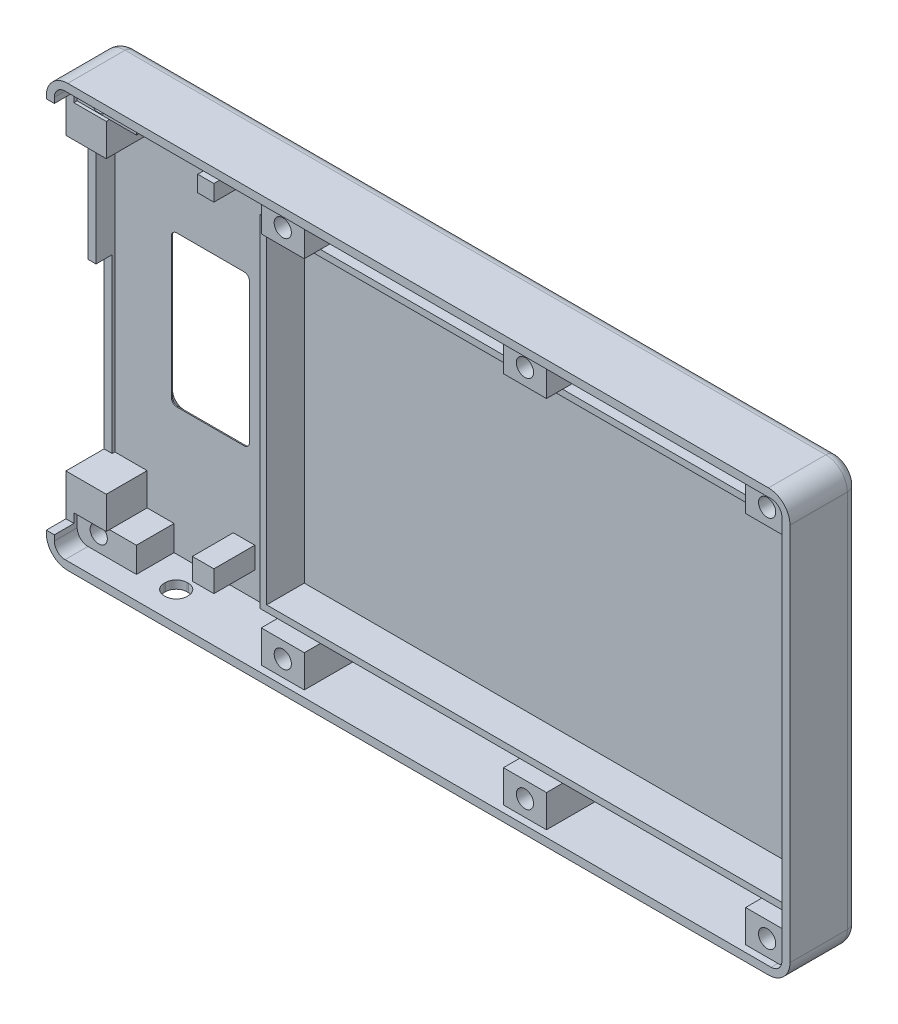
SolidWorks part; units mm, degrees
ref_plane "Plan de face" through (0, 0, 0) normal (0, 0, 1) x (1, 0, 0)
ref_plane "Plan de dessus" through (0, 0, 0) normal (0, 1, 0) x (1, 0, 0)
ref_plane "Plan de droite" through (0, 0, 0) normal (1, 0, 0) x (0, 0, -1)
sketch "Esquisse1" plane through (0, 0, 0) normal (0, 0, 1) x (1, 0, 0)
  line L0 (135.2, 69.4) -> (34, 69.4)
  line L1 (0, 0) -> (135.2, 0)
  line L2 (0, 0) -> (0, 75.4)
  line L3 (0, 75.4) -> (135.2, 75.4)
  line L4 (135.2, 0) -> (135.2, 75.4)
  line L5 (34, 69.4) -> (34, 6)
  line L6 (34, 6) -> (135.2, 6)
  line L7 (135.2, 68.2) -> (35.2, 68.2)
  line L8 (35.2, 68.2) -> (35.2, 7.2)
  line L9 (35.2, 7.2) -> (135.2, 7.2)
  line L10 (-19.055, 37.7) -> (204.5006, 37.7) construction
  line L11 (-1.5, 76.9) -> (136.7, 76.9)
  line L12 (-1.5, 76.9) -> (-1.5, -1.5)
  line L13 (-1.5, -1.5) -> (136.7, -1.5)
  line L14 (136.7, 76.9) -> (136.7, -1.5)
  line L15 (0, 72.1) -> (0, 70.7)
  line L16 (26, 70.7) -> (0, 70.7)
  line L17 (26, 70.7) -> (26, 4.7)
  line L18 (26, 4.7) -> (0, 4.7)
  line L19 (0, 70.7) -> (0, 4.7)
  line L20 (1.4, 69.3) -> (24.6, 69.3)
  line L21 (1.4, 69.3) -> (1.4, 6.1)
  line L22 (1.4, 6.1) -> (24.6, 6.1)
  line L23 (24.6, 69.3) -> (24.6, 6.1)
  line L24 (0, 72.1) -> (27.4, 72.1)
  line L25 (0, 3.3) -> (0, 4.7)
  line L26 (0, 3.3) -> (27.4, 3.3)
  line L27 (27.4, 72.1) -> (27.4, 3.3)
  line L28 (127.2, 75.4) -> (127.2, 69.4)
  line L29 (0, 4.7) -> (6, 4.7)
  line L30 (0, 4.7) -> (0, 10.7)
  line L31 (0, 10.7) -> (6, 10.7)
  line L32 (6, 4.7) -> (6, 10.7)
  line L33 (26, 4.7) -> (22, 4.7)
  line L34 (26, 4.7) -> (26, 8.7)
  line L35 (26, 8.7) -> (22, 8.7)
  line L36 (22, 4.7) -> (22, 8.7)
  line L37 (0, 70.7) -> (6, 70.7)
  line L38 (0, 70.7) -> (0, 64.7)
  line L39 (0, 64.7) -> (6, 64.7)
  line L40 (6, 70.7) -> (6, 64.7)
  line L41 (26, 70.7) -> (23, 70.7)
  line L42 (26, 70.7) -> (26, 67.7)
  line L43 (26, 67.7) -> (23, 67.7)
  line L44 (23, 70.7) -> (23, 67.7)
  line L45 (90.2, 75.4) -> (90.2, 69.4)
  line L46 (82.2, 75.4) -> (82.2, 69.4)
  line L47 (45.2, 75.4) -> (45.2, 69.4)
  line L48 (37.2, 75.4) -> (37.2, 69.4)
  line L49 (127.2, 0) -> (127.2, 6)
  line L50 (90.2, 0) -> (90.2, 6)
  line L51 (82.2, 0) -> (82.2, 6)
  line L52 (45.2, 0) -> (45.2, 6)
  line L53 (37.2, 0) -> (37.2, 6)
  circle A0 centre (131.2, 72.4) radius 1.25
  circle A3 centre (86.2, 72.4) radius 1.25
  circle A5 centre (41.2, 72.4) radius 1.25
  circle A6 centre (131.2, 3) radius 1.25
  circle A8 centre (86.2, 3) radius 1.25
  circle A11 centre (41.2, 3) radius 1.25
  dimension "D12" = 2.5
  dimension "D13" = 4
  dimension "D1" = 1.5
  dimension "D3" = 1.2
  dimension "D4" = 1.2
  dimension "D5" = 1.2
  dimension "D6" = 61
  dimension "D7" = 6
  dimension "D8" = 100
  dimension "D9" = 1.5
  dimension "D10" = 1.5
  dimension "D11" = 1.5
  dimension "D15" = 30.5
  dimension "D16" = 30.5
  dimension "D17" = 3
  dimension "D18" = 66
  dimension "D19" = 26
  dimension "D20" = 33
  dimension "D21" = 33
  dimension "D22" = 8
  dimension "D23" = 1.4
  dimension "D24" = 1.4
  dimension "D25" = 1.4
  dimension "D26" = 1.4
  dimension "D27" = 1.4
  dimension "D28" = 0
  dimension "D29" = 1.4
  dimension "D30" = 1.4
  dimension "D31" = 4
  dimension "D32" = 0
  dimension "D33" = 0
  dimension "D34" = 6
  dimension "D35" = 6
  dimension "D36" = 4
  dimension "D37" = 4
  dimension "D38" = 6
  dimension "D39" = 6
  dimension "D40" = 3
  dimension "D41" = 3
  dimension "D42" = 4
  dimension "D43" = 4
  dimension "D44" = 4
  dimension "D45" = 4
  dimension "D46" = 6
  dimension "D47" = 45
  dimension "D14" = 3
extrude "Boss.-Extru.1" add sketch "Esquisse1" along normal blind 12.65 contours L12 L10 L2 L3 L4 L14 L11 | L10 L12 L13 L14 L4 L1 L2 region at (136.6365, 72.4, 0) region at (135.95, 36.2635, 0)
extrude "Boss.-Extru.2" add sketch "Esquisse1<4>" along normal blind 1.4 contours L3 L4 L1 L2
sketch "Esquisse1<4>" plane through (0, 0, 0) normal (0, 0, 1) x (1, 0, 0) same geometry as "Esquisse1"
extrude "Boss.-Extru.5" add sketch "Esquisse1<5>" along normal blind 10 from surface separate body contours A5 | A3 | A0 | A11 | A8 | A6 region at (131.2, 69.5, 0) region at (86.2, 69.5, 0) region at (135.1, 3, 0) region at (41.2, 69.5, 0) region at (90.1, 3, 0) region at (45.1, 3, 0) starting at face at (67.6, 37.7, 1.4)
sketch "Esquisse1<5>" plane through (0, 0, 0) normal (0, 0, 1) x (1, 0, 0) same geometry as "Esquisse1"
extrude "Boss.-Extru.7" add sketch "Esquisse1<6>" along normal blind 7 from surface contours L5 L10 L8 L7 L4 L0 | L10 L5 L6 L4 L9 L8 region at (134.1395, 68.8, 0) region at (134.1395, 6.6, 0) starting at face at (67.6, 37.7, 1.4)
sketch "Esquisse1<6>" plane through (0, 0, 0) normal (0, 0, 1) x (1, 0, 0) same geometry as "Esquisse1"
fillet "Congé1" radius 4 4 edges at (-1.5, 76.9, 6.325) (-1.5, -1.5, 6.325) (136.7, -1.5, 6.325) (136.7, 76.9, 6.325)
fillet "Congé2" radius 2 4 edges at (0, 0, 7.025) (135.2, 0, 7.025) (135.2, 75.4, 7.025) (0, 75.4, 7.025)
sketch "Esquisse4" plane through (0, 0, 0) normal (0, 0, -1) x (-1, 0, 0)
  circle A0 centre (-41.2, 3) radius 1.6
  circle A1 centre (-86.2, 3) radius 1.6
  circle A2 centre (-131.2, 3) radius 1.6
  circle A3 centre (-131.2, 72.4) radius 1.6
  circle A4 centre (-86.2, 72.4) radius 1.6
  circle A5 centre (-41.2, 72.4) radius 1.6
  dimension "D1" = 3.2
  dimension "D2" = 3.2
  dimension "D3" = 3.2
  dimension "D4" = 3.2
  dimension "D5" = 3.2
  dimension "D6" = 3.2
extrude "Enlèv. mat.-Extru.2" cut sketch "Esquisse4" against normal blind 60.5 and the other way blind 4.3
extrude "Boss.-Extru.9" add sketch "Esquisse1<9>" along normal blind 7.6 from surface contours L38 L39 L40 L37 | L42 L43 L44 L41 | L30 L31 L32 L29 | L34 L35 L36 L33 starting at face at (84.6, 3, 1.4)
sketch "Esquisse1<9>" plane through (0, 0, 0) normal (0, 0, 1) x (1, 0, 0) same geometry as "Esquisse1"
sketch "Esquisse5" plane through (0, 0, 1.4) normal (0, 0, 1) x (1, 0, 0)
  line L1 (11, 70.7) -> (0, 70.7)
  line L2 (11, 70.7) -> (11, 75.4)
  line L3 (11, 75.4) -> (0, 75.4)
  line L4 (0, 70.7) -> (0, 75.4)
  line L5 (11, 4.7) -> (0, 4.7)
  line L6 (11, 4.7) -> (11, 0)
  line L7 (11, 0) -> (0, 0)
  line L8 (0, 4.7) -> (0, 0)
  line L9 (2, 75.4) -> (133.2, 75.4) construction
  line L10 (0, 4.7) -> (6, 4.7) construction
  line L11 (0, 70.7) -> (6, 70.7) construction
  dimension "D1" = 0
  dimension "D2" = 0
  dimension "D3" = 0
  dimension "D4" = 11
  dimension "D5" = 11
extrude "Boss.-Extru.10" add sketch "Esquisse5" along normal blind 7
sketch "Esquisse6" plane through (0, 0, 0) normal (0, 0, -1) x (-1, 0, 0)
  line L7 (-11, 70.7) -> (-11, 75.4) construction
  line L8 (-11, 0) -> (-11, 4.7) construction
  circle A0 centre (-4, 3) radius 1.6
  circle A1 centre (-4, 72.4) radius 1.6
  circle A2 centre (-41.2, 72.4) radius 1.6 construction
  circle A3 centre (-41.2, 3) radius 1.6 construction
  dimension "D1" = 3.2
  dimension "D2" = 3.2
  dimension "D3" = 7
  dimension "D4" = 0
  dimension "D5" = 7
  dimension "D6" = 0
extrude "Enlèv. mat.-Extru.3" cut sketch "Esquisse6" against normal blind 40
chamfer "Chanfrein3" distance 1.48 angle 45 8 edges at (2.4, 3, 0) (2.4, 72.4, 0) (42.8, 3, 0) (87.8, 3, 0) (132.8, 3, 0) (132.8, 72.4, 0) (87.8, 72.4, 0) (42.8, 72.4, 0)
sketch "Esquisse9" plane through (0, 0, 0) normal (0, 0, -1) x (-1, 0, 0)
  line L0 (1.5, 72.9) -> (1.5, 2.5) construction
  line L1 (-11.5, 23.7) -> (-24, 23.7)
  line L2 (-10.5, 24.7) -> (-10.5, 50.7)
  line L3 (-11.5, 51.7) -> (-24, 51.7)
  line L4 (-25, 24.7) -> (-25, 50.7)
  line L5 (-2.5, -1.5) -> (-132.7, -1.5) construction
  line L6 (-2.5, 76.9) -> (-132.7, 76.9) construction
  arc A0 (-10.5, 50.7) -> (-11.5, 51.7) centre (-11.5, 50.7) ccw
  arc A1 (-24, 51.7) -> (-25, 50.7) centre (-24, 50.7) ccw
  arc A2 (-24, 23.7) -> (-25, 24.7) centre (-24, 24.7) cw
  arc A3 (-11.5, 23.7) -> (-10.5, 24.7) centre (-11.5, 24.7) ccw
  point P12 (-10.5, 51.7)
  point P15 (-25, 51.7)
  point P20 (-10.5, 23.7)
  dimension "D6" = 1
  dimension "D1" = 28
  dimension "D2" = 14.5
  dimension "D3" = 12
  dimension "D4" = 25.2
  dimension "D5" = 25.2
extrude "Enlèv. mat.-Extru.6" cut sketch "Esquisse9" against normal blind 1.4
sketch "Esquisse10" plane through (0, -1.5, 0) normal (0, -1, 0) x (1, 0, 0)
  line L1 (17.25, 9.25) -> (17, 9.25)
  line L2 (19.25, 7.25) -> (19.25, 7)
  line L3 (17.25, 5) -> (17, 5)
  line L4 (15, 7.25) -> (15, 7)
  line L9 (0, 9) -> (6, 9) construction
  line L10 (2.5, 12.65) -> (2.5, 0) construction
  arc A0 (17.25, 9.25) -> (19.25, 7.25) centre (17.25, 7.25) cw
  arc A1 (19.25, 7) -> (17.25, 5) centre (17.25, 7) cw
  arc A2 (17, 5) -> (15, 7) centre (17, 7) cw
  arc A3 (17, 9.25) -> (15, 7.25) centre (17, 7.25) ccw
  point P12 (19.25, 5)
  point P15 (15, 5)
  dimension "D5" = 2
  dimension "D1" = 4.25
  dimension "D2" = 4
  dimension "D3" = 12.5
  dimension "D4" = 4.25
extrude "Enlèv. mat.-Extru.7" cut sketch "Esquisse10" against normal blind 3
chamfer "Chanfrein4" distance 1.2 angle 45 8 edges at (10.5, 37.7, 0) (10.7929, 51.4071, 0) (10.7929, 23.9929, 0) (17.75, 51.7, 0) (17.75, 23.7, 0) (24.7071, 51.4071, 0) (24.7071, 23.9929, 0) (25, 37.7, 0)
fillet "Congé3" radius 2 8 edges at (-0.3284, -0.3284, 0) (-1.5, 37.7, 0) (-0.3284, 75.7284, 0) (67.6, 76.9, 0) (135.5284, 75.7284, 0) (136.7, 37.7, 0) (135.5284, -0.3284, 0) (67.6, -1.5, 0)
sketch "Esquisse11" plane through (0, 0, 12.65) normal (0, 0, 1) x (1, 0, 0)
  line L0 (-1.5, 72.9) -> (-1.5, 2.5) construction
  line L1 (0, 64.7) -> (-1.5, 64.7)
  line L2 (0, 64.7) -> (0, 72.4)
  line L3 (0, 72.4) -> (-1.5, 72.4)
  line L4 (-1.5, 64.7) -> (-1.5, 72.4)
  line L6 (0, 10.7) -> (-1.5, 10.7)
  line L7 (0, 10.7) -> (0, 3)
  line L8 (0, 3) -> (-1.5, 3)
  line L9 (-1.5, 10.7) -> (-1.5, 3)
  dimension "D1" = 7.7
  dimension "D2" = 7.7
sketch "Esquisse12" plane through (0, 0, 12.65) normal (0, 0, 1) x (1, 0, 0)
  line L1 (0, 10.7) -> (-1.5, 10.7)
  line L2 (0, 10.7) -> (0, 42.7)
  line L3 (0, 42.7) -> (-1.5, 42.7)
  line L4 (-1.5, 10.7) -> (-1.5, 42.7)
  dimension "D1" = 32
extrude "Enlèv. mat.-Extru.8" cut sketch "Esquisse12" against normal blind 10.75
sketch "Esquisse13" plane through (0, 0, 12.65) normal (0, 0, 1) x (1, 0, 0)
  line L1 (-1.5, 42.7) -> (0, 42.7)
  line L2 (-1.5, 42.7) -> (-1.5, 64.7)
  line L3 (-1.5, 64.7) -> (0, 64.7)
  line L4 (0, 42.7) -> (0, 64.7)
extrude "Enlèv. mat.-Extru.9" cut sketch "Esquisse13" against normal blind 7.75
extrude "Enlèv. mat.-Extru.10" cut sketch "Esquisse11" against normal blind 3.65
